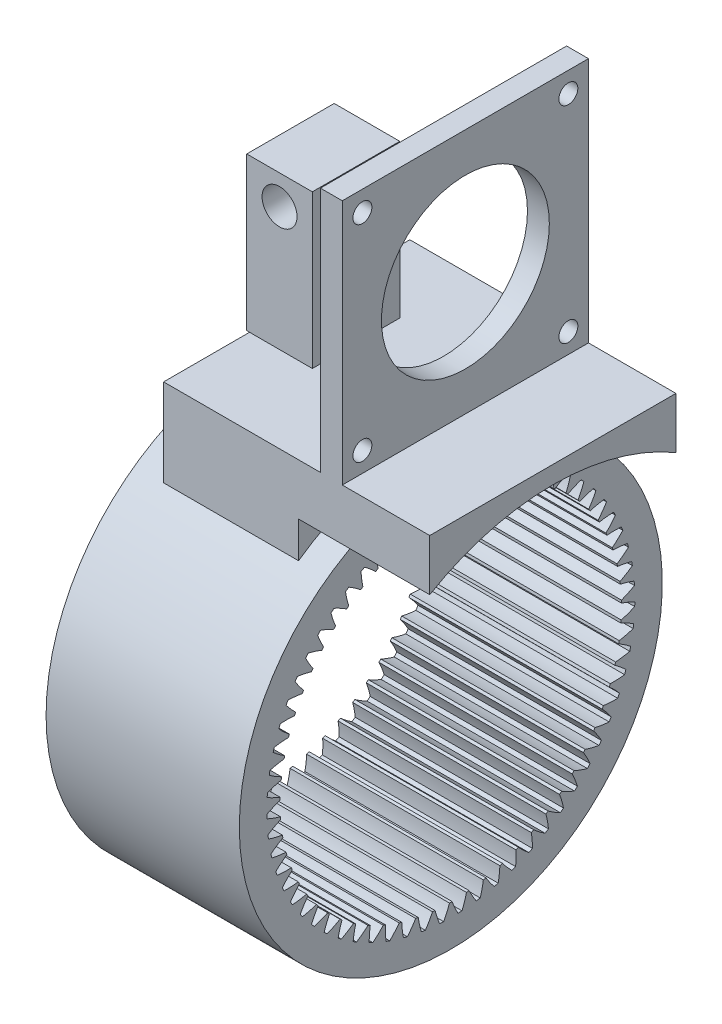
SolidWorks part; units mm, degrees
ref_plane "Plane1" through (0, 0, 0) normal (0, 0, 1) x (1, 0, 0)
ref_plane "Plane2" through (0, 0, 0) normal (0, 1, 0) x (1, 0, 0)
ref_plane "Plane3" through (0, 0, 0) normal (1, 0, 0) x (0, 0, -1)
sketch "HoldingSke" plane through (0, 0, 0) normal (0, 1, 0) x (1, 0, 0)
  line L0 (0, 0) -> (0.5, -0.866)
  line L1 (-15, 0) -> (100, 0) construction
  line L2 (0, 0) -> (-2.1039, 2.3779)
  line L3 (0, 0) -> (-11.863, 4.5341)
  line L4 (0, 0) -> (4.318, 7.479)
  line L5 (0, 0) -> (-23.7986, -8.8762)
  line L6 (0, 0) -> (-10.5278, -7.1032)
  line L7 (-2.1039, 2.3779) -> (3.3635, 27.1825)
  line L8 (-76.2, 3.3779) -> (-54.61, 3.3779)
  line L9 (-71.009, 38.7566) -> (-53.1078, 45.2721)
  line L10 (-76.2, 71.12) -> (104.1128, 71.12)
  line L11 (0, 0) -> (-12, 0)
  line L12 (-76.2, 101.6) -> (-76.162, 101.6)
  line L13 (24.9733, 27.94) -> (52.9518, 28.4284)
  line L14 (24.9733, 27.94) -> (24.9743, 27.94)
  line L15 (24.9733, 27.94) -> (100.4006, 29.5858)
  circle A0 centre (0, 0) radius 12.5
  circle A1 centre (0, 0) radius 12.7
  circle A2 centre (0, 0) radius 12.7
  dimension "MHD" = 25.4
  dimension "Hub_dia" = 25.4
  dimension "Diameter" = 25
  dimension "Num_teeth" = 60
  dimension "Pitch" = 1
  dimension "Overall_len" = 25.4
  dimension "Show_teeth" = 60
  dimension "Thickness" = 12.7
  dimension "OAL" = 25.4001
  dimension "T_dim" = 21.59
  dimension "Ap" = 20
  dimension "H" = 19.05
  dimension "Pitch_radius" = 180.3128
  dimension "Width" = 12
  dimension "Backlash" = 0.038
  dimension "Addendum_fac" = 1
  dimension "Dedendum_fac" = 1.25
  dimension "Clearance_fac" = 0.25
  dimension "Dedendum_add" = 0.001
  dimension "Module" = 1
sketch "BasProSke" plane through (0, 0, 0) normal (0, 1, 0) x (1, 0, 0)
  line L0 (-10, 0) -> (60, 0) construction
  line L1 (0, 29) -> (0, 31.2764)
  line L2 (0, 29) -> (32.815, 29)
  line L3 (32.815, 29) -> (32.815, 31.2764)
  line L4 (32.815, 31.2764) -> (0, 31.2764)
  dimension "Thickness" = 32.815
  dimension "Diameter" = 62.5528
  dimension "Inside_diameter" = 58
revolve "Base-Revolve" add sketch "BasProSke" angle 360 about L0
sketch "TooCutSke" plane through (0, 0, 0) normal (1, 0, 0) x (0, 0, -1)
  line L3 (0.8803, 29.9871) -> (0.8803, 53.6633) construction
  line L4 (0, 0) -> (0, 59.563) construction
  line L5 (0, 0) -> (-3.576, 68.2339) construction
  line L6 (-13.1633, 24.7167) -> (36.4631, 27.3175) construction
  circle A0 centre (0, 0) radius 30 construction
  circle A1 centre (0, 0) radius 31.251 construction
  circle A2 centre (0, 0) radius 25.3717 construction
  circle A3 centre (0, 0) radius 28.9746 construction
  arc A4 (1.2274, 28.9486) -> (0.3395, 31.2492) centre (-13.1633, 24.7167) ccw
  arc A5 (1.2274, 28.9486) -> (-1.2274, 28.9486) centre (0, 0) ccw
  arc A6 (0.3395, 31.2492) -> (-0.3395, 31.2492) centre (0, 0) ccw
  arc A7 (-0.3395, 31.2492) -> (-1.2274, 28.9486) centre (13.1633, 24.7167) ccw
  dimension "Pitch_dia" = 60
  dimension "Base_dia" = 50.7434
  dimension "Root_dia" = 62.502
  dimension "Overcut_dia" = 57.9492
  dimension "Flank_rad" = 15
  dimension "Half_ang" = 3
  dimension "Half_CT" = 0.8803
extrude "ToothCut" cut sketch "TooCutSke" along normal through all
fillet "Breaks" [suppressed] radius 0.1
fillet "RootFillets" [suppressed] radius 0.251
pattern_circular "TeethCuts" count 63 over 360 about axis through (-10, 0, 0) along (1, 0, 0) of "ToothCut"
scale "Scale1" scale about centroid uniform scaling yes scale factor 2
sketch "Sketch1" plane through (49.2225, 0, 0) normal (1, 0, 0) x (0, 0, -1)
  circle A0 centre (0, 0) radius 62.5528
sketch "Sketch2" plane through (49.2225, 0, 0) normal (1, 0, 0) x (0, 0, -1)
  circle A0 centre (0, 0) radius 72.5528
  circle A1 centre (0, 0) radius 62.5528
extrude "Boss-Extrude1" add sketch "Sketch2" against normal blind 65.63
scale "Scale2" scale about centroid uniform scaling yes scale factor 1.1
scale "Scale3" scale about centroid uniform scaling yes scale factor 1.01
scale "Scale4" scale about centroid uniform scaling yes scale factor 0.990099
scale "Scale5" scale about centroid uniform scaling yes scale factor 0.909091
scale "Scale6" scale about centroid uniform scaling yes scale factor 1.01
sketch "Sketch3" plane through (-16.7356, 0, 0) normal (-1, 0, 0) x (0, 0, 1)
  circle A0 centre (0, 0) radius 72.5528
  circle A1 centre (0, 0) radius 73.2783
extrude "Cut-Extrude1" cut sketch "Sketch3" against normal through all
ref_plane "Plane4" through (39.5507, 0, 0) normal (1, 0, 0) x (0, 0, -1)
sketch "Sketch4" plane through (39.5507, 0, 0) normal (1, 0, 0) x (0, 0, -1)
  line L10 (-42.225, 88.9996) -> (-42.225, 58.9996)
  line L11 (42.225, 88.9996) -> (42.225, 58.9996)
  line L12 (0, 0) -> (-42.225, 58.9996) construction
  line L13 (42.225, 58.9996) -> (0, 0) construction
  line L18 (42.225, 88.9996) -> (-42.225, 88.9996)
  arc A0 (42.225, 58.9996) -> (-42.225, 58.9996) centre (0, 0) ccw
  circle A1 centre (0, 0) radius 72.5528 construction
  point P12 (0, 72.5528)
  dimension "D1" = 84.45
  dimension "D3" = 30
extrude "Boss-Extrude2" add sketch "Sketch4" against normal blind 46.2863
scale "Scale7" scale about centroid uniform scaling yes scale factor 0.666667
sketch "Sketch17" plane through (31.8363, 0, 0) normal (1, 0, 0) x (0, 0, -1)
  line L1 (-28.15, 64.6246) -> (-28.15, 44.6246) construction
  line L4 (-28.15, 52.8966) -> (-28.15, 64.6246)
  line L5 (-28.15, 64.6246) -> (28.15, 64.6246)
  line L6 (28.15, 64.6246) -> (28.15, 52.8966)
  arc A1 (28.15, 52.8966) -> (-28.15, 52.8966) centre (0, 5.2915) ccw
  circle A2 centre (0, 5.2915) radius 48.3685 construction
  dimension "D1" = 110.6104
extrude "Boss-Extrude3" add sketch "Sketch17" along normal blind 30
ref_plane "Plane5" through (16.4075, 0, 0) normal (1, 0, 0) x (0, 0, -1)
ref_plane "Plane6" through (41.8363, 0, 0) normal (1, 0, 0) x (0, 0, -1)
sketch "Sketch18" plane through (41.8363, 0, 0) normal (1, 0, 0) x (0, 0, -1)
  line L0 (28.15, 52.8966) -> (28.15, 64.6246) construction
  line L1 (-28.15, 64.6246) -> (28.15, 64.6246)
  line L2 (-28.15, 64.6246) -> (-28.15, 120.9246)
  line L3 (-28.15, 120.9246) -> (28.15, 120.9246)
  line L4 (28.15, 64.6246) -> (28.15, 120.9246)
  line L6 (23.55, 69.1773) -> (-23.55, 69.1773) construction
  line L7 (23.55, 69.1773) -> (23.55, 116.2773) construction
  line L8 (23.55, 116.2773) -> (-23.55, 116.2773) construction
  line L9 (-23.55, 69.1773) -> (-23.55, 116.2773) construction
  line L10 (23.55, 69.1773) -> (-23.55, 116.2773) construction
  line L11 (23.55, 116.2773) -> (-23.55, 69.1773) construction
  circle A1 centre (-23.55, 116.2773) radius 2.165
  circle A2 centre (23.55, 116.2773) radius 2.165
  circle A3 centre (-23.55, 69.1773) radius 2.165
  circle A4 centre (23.55, 69.1773) radius 2.165
  circle A5 centre (0, 92.7273) radius 19.2
  dimension "D2" = 38.4
  dimension "D1" = 56.3
  dimension "D4" = 47.1
  dimension "D5" = 47.1
extrude "Boss-Extrude4" add sketch "Sketch18" against normal blind 5
ref_plane "Plane7" through (0, 0, -1.5) normal (0, 0, 1) x (1, 0, 0)
sketch "Sketch19" plane through (0, 0, -1.5) normal (0, 0, 1) x (1, 0, 0)
  line L0 (36.8363, 64.6246) -> (7.8363, 64.6246) construction
  line L1 (0.9787, 64.6246) -> (36.8363, 64.6246) construction
  line L2 (7.8363, 64.6246) -> (7.8363, 92.9185) construction
  line L4 (0.3363, 99.6246) -> (15.3363, 99.6246)
  line L5 (0.3363, 99.6246) -> (0.3363, 64.6246)
  line L6 (0.3363, 64.6246) -> (15.3363, 64.6246)
  line L7 (15.3363, 99.6246) -> (15.3363, 64.6246)
  line L8 (0.3363, 99.6246) -> (15.3363, 64.6246) construction
  line L9 (0.3363, 64.6246) -> (15.3363, 99.6246) construction
  circle A0 centre (7.8363, 92.9185) radius 4
  point P5 (7.8363, 82.1246)
  dimension "D5" = 8
  dimension "D1" = 29
  dimension "D2" = 28.2939
  dimension "D3" = 15
  dimension "D4" = 35
extrude "Boss-Extrude5" add sketch "Sketch19" along normal mid plane 20
equation "' \"Module@HoldingSke\" = 6.35"
equation "' \"Num_teeth@HoldingSke\" = 24"
equation "' \"Ap@HoldingSke\" =  14.5"
equation "' \"Ap@HoldingSke\" = 14.5"
equation "' \"Width@HoldingSke\" = 12"
equation "' \"Diameter@HoldingSke\" = 8 * 25.4"
equation "' \"Show_teeth@HoldingSke\" = 100"
equation "' \"Backlash@HoldingSke\" = 0.009 * 25.4"
equation "' \"Addendum_fac@HoldingSke\" = 1.0"
equation "' \"Dedendum_fac@HoldingSke\" = 1.25"
equation "' \"Dedendum_add@HoldingSke\" = 0.00005 * 25.4"
equation "' \"Clearance_fac@HoldingSke\" = 0.25"
equation "\"Pitch@HoldingSke\" = 1 / \"Module@HoldingSke\" "
equation "\"Overcut_dia@TooCutSke\" = (\"Num_teeth@HoldingSke\" - 2 * \"Addendum_fac@HoldingSke\") / \"Pitch@HoldingSke\" - 0.002 * 25.4"
equation "\"Pitch_dia@TooCutSke\" = \"Num_teeth@HoldingSke\" / \"Pitch@HoldingSke\""
equation "\"Base_dia@TooCutSke\" = \"Num_teeth@HoldingSke\" / \"Pitch@HoldingSke\" * cos((\"Ap@HoldingSke\"  * 3.14159265 / 180)) * 0.90"
equation "\"Root_dia@TooCutSke\" = \"Num_teeth@HoldingSke\"  / \"Pitch@HoldingSke\" + 2 *  \"Dedendum_fac@HoldingSke\"/ \"Pitch@HoldingSke\" + \"Dedendum_add@HoldingSke\" * 2"
equation "\"Half_ang@TooCutSke\" = 180 / \"Num_teeth@HoldingSke\""
equation "\"Half_CT@TooCutSke\" = \"Num_teeth@HoldingSke\" / \"Pitch@HoldingSke\" * sin((3.14159265 / 2 / \"Num_teeth@HoldingSke\")) / 2 + 10 * \"Backlash@HoldingSke\" / 4"
equation "\"Flank_rad@TooCutSke\" = \"Num_teeth@HoldingSke\" / \"Pitch@HoldingSke\" / 4"
equation "\"Radius@RootFillets\"= \"Clearance_fac@HoldingSke\" / \"Pitch@HoldingSke\" + \"Dedendum_add@HoldingSke\""
equation "\"Break_rad@Breaks\" = 0.02 / \"Pitch@HoldingSke\" * 5"
equation "\"Diameter@BasProSke\" = \"Num_teeth@HoldingSke\"  / \"Pitch@HoldingSke\" + 2 *  \"Dedendum_fac@HoldingSke\"/ \"Pitch@HoldingSke\" + \"Dedendum_add@HoldingSke\" * 2 + 0.002 * 25.4"
equation "\"Diameter@BasProSke\" = ((sgn( \"Diameter@BasProSke\"  - \"Diameter@HoldingSke\" )+1)*( \"Diameter@BasProSke\"  - \"Diameter@HoldingSke\" ))/2 + \"Diameter@HoldingSke\""
equation "\"Inside_diameter@BasProSke\" =  (\"Num_teeth@HoldingSke\" - 2 * \"Addendum_fac@HoldingSke\") / \"Pitch@HoldingSke\" "
